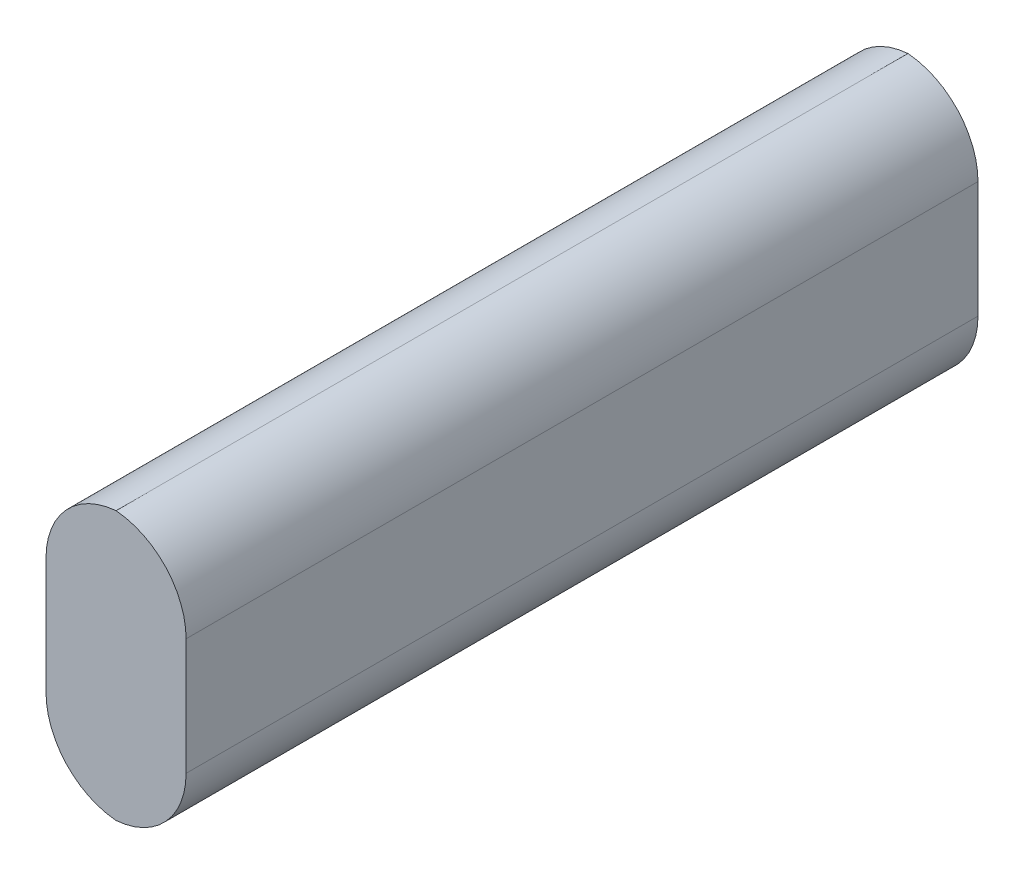
SolidWorks part; units mm, degrees
ref_plane "Front Plane" through (0, 0, 0) normal (0, 0, 1) x (1, 0, 0)
ref_plane "Top Plane" through (0, 0, 0) normal (0, 1, 0) x (1, 0, 0)
ref_plane "Right Plane" through (0, 0, 0) normal (1, 0, 0) x (0, 0, -1)
sketch "Sketch1" plane through (0, 0, 0) normal (0, 0, 1) x (1, 0, 0)
  line L1 (11.684, -22.4155) -> (-11.684, -22.4155)
  line L2 (11.684, -22.4155) -> (11.684, 22.4155)
  line L3 (11.684, 22.4155) -> (-11.684, 22.4155)
  line L4 (-11.684, -22.4155) -> (-11.684, 22.4155)
  line L5 (11.684, -22.4155) -> (-11.684, 22.4155) construction
  line L6 (11.684, 22.4155) -> (-11.684, -22.4155) construction
  point P0 (0, 0)
  dimension "D1" = 23.368
  dimension "D2" = 44.831
extrude "Boss-Extrude1" add sketch "Sketch1" along normal blind 132.08
fillet "Fillet1" radius 12.7 4 edges at (11.684, -22.4155, 66.04) (-11.684, -22.4155, 66.04) (-11.684, 22.4155, 66.04) (11.684, 22.4155, 66.04)
